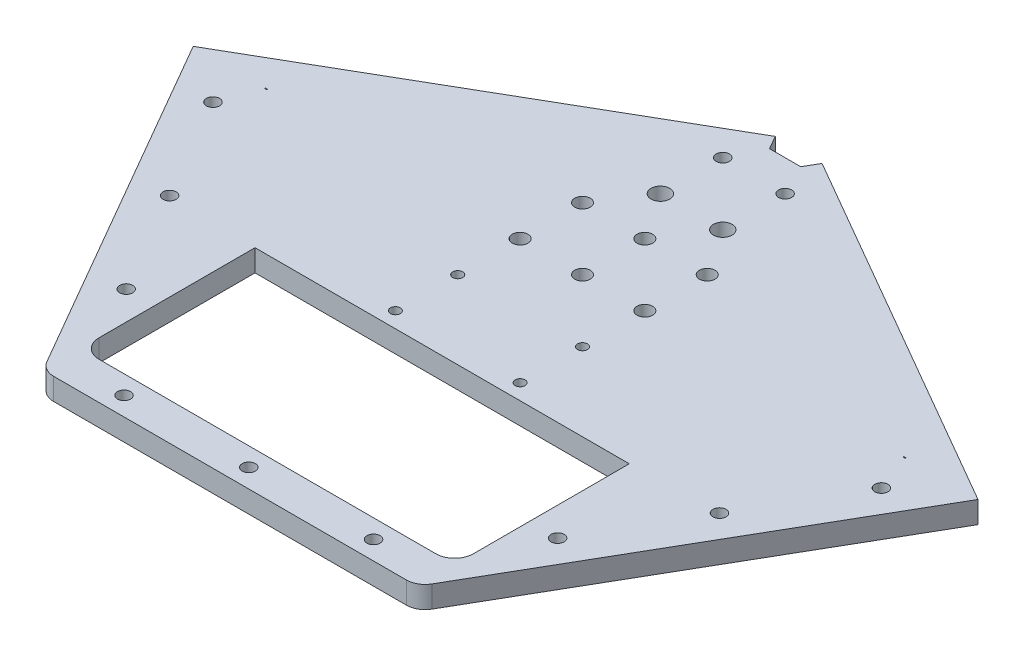
SolidWorks part; units mm, degrees
ref_plane "Front Plane" through (0, 0, 0) normal (0, 0, 1) x (1, 0, 0)
ref_plane "Top Plane" through (0, 0, 0) normal (0, 1, 0) x (1, 0, 0)
ref_plane "Right Plane" through (0, 0, 0) normal (1, 0, 0) x (0, 0, -1)
sketch "Sketch1" plane through (0, 0, 0) normal (0, 1, 0) x (1, 0, 0)
  line L15 (0, 28) -> (0, 74) construction
  line L16 (-60, -28) -> (60, -28)
  line L17 (-60, -28) -> (-60, 28)
  line L18 (-60, 28) -> (60, 28)
  line L19 (60, -28) -> (60, 28)
  line L20 (-60, -28) -> (60, 28) construction
  line L21 (-60, 28) -> (60, -28) construction
  line L27 (-20, 53) -> (-20, 33) construction
  line L31 (-20, 33) -> (0, 33) construction
  line L32 (-60, -40) -> (60, -40)
  line L33 (0, -40) -> (0, -28) construction
  line L34 (-60, -40) -> (-125.8179, 74)
  line L35 (-125.8179, 74) -> (125.8179, 74)
  line L36 (-125.8179, 74) -> (-191.6359, 188) construction
  line L37 (-191.6359, 188) -> (-131.6359, 291.923) construction
  line L38 (131.6359, 291.923) -> (191.6359, 188) construction
  line L39 (125.8179, 74) -> (191.6359, 188) construction
  line L40 (60, -40) -> (125.8179, 74)
  line L41 (87.7128, 48) -> (30, 48)
  line L42 (-131.6359, 291.923) -> (0, 291.923) construction
  line L48 (-125.8179, 74) -> (-108.4974, 84)
  line L49 (-108.4974, 84) -> (-87.7128, 48)
  line L50 (-87.7128, 48) -> (-30, 48)
  line L51 (-30, 48) -> (-30, 74)
  line L53 (-117.1577, 79) -> (-51.9171, -34) construction
  line L54 (-51.9171, -34) -> (0, -34) construction
  line L55 (0, 291.923) -> (131.6359, 291.923) construction
  line L62 (125.8179, 74) -> (108.4974, 84)
  line L63 (108.4974, 84) -> (87.7128, 48)
  line L64 (-161.6359, 239.9615) -> (0, 146.641) construction
  line L65 (-10, 107.9808) -> (10, 107.9808)
  line L66 (-10, 107.9808) -> (-10, 127.9808)
  line L67 (-10, 127.9808) -> (10, 127.9808)
  line L68 (10, 107.9808) -> (10, 127.9808)
  line L69 (-10, 107.9808) -> (10, 127.9808) construction
  line L70 (-10, 127.9808) -> (10, 107.9808) construction
  line L71 (0, 146.641) -> (161.6359, 239.9615) construction
  line L72 (30, 48) -> (30, 74)
  line L73 (0, 146.641) -> (0, -40) construction
  line L74 (-20, 112) -> (0, 146.641) construction
  line L75 (-20, 112) -> (20, 112)
  line L76 (20, 112) -> (40, 146.641)
  line L77 (40, 146.641) -> (20, 181.282)
  line L78 (20, 181.282) -> (-20, 181.282)
  line L79 (-20, 181.282) -> (-40, 146.641)
  line L80 (-40, 146.641) -> (-20, 112)
  line L81 (0, 146.641) -> (20, 181.282) construction
  line L82 (-20, 181.282) -> (0, 146.641) construction
  line L83 (0, 146.641) -> (20, 112) construction
  line L84 (-40, 146.641) -> (40, 146.641) construction
  line L85 (-30, 129.3205) -> (0, 146.641)
  line L86 (0, 146.641) -> (30, 129.3205)
  line L87 (0, 146.641) -> (0, 181.282) construction
  line L88 (-30, 129.3205) -> (-30, 74)
  line L89 (5, 137.9808) -> (10, 146.641)
  line L90 (10, 146.641) -> (5, 155.3013)
  line L91 (5, 155.3013) -> (-5, 155.3013)
  line L92 (-5, 155.3013) -> (-10, 146.641)
  line L93 (-10, 146.641) -> (-5, 137.9808)
  line L94 (-5, 137.9808) -> (5, 137.9808)
  line L95 (30, 129.3205) -> (30, 74)
  line L96 (-108.4974, 84) -> (-30, 129.3205)
  line L97 (-30, 115.4641) -> (-102.4974, 73.6077)
  line L98 (30, 129.3205) -> (108.4974, 84)
  line L99 (30, 115.4641) -> (102.4974, 73.6077)
  line L100 (-20, 73) -> (0, 73)
  line L101 (0, 73) -> (20, 73)
  line L102 (20, 73) -> (20, 93)
  line L103 (20, 93) -> (0, 93)
  line L104 (0, 93) -> (-20, 93)
  line L105 (-72.8179, -17.7987) -> (-55.4974, -7.7987) construction
  line L106 (-55.4974, -7.7987) -> (-55.4974, 28) construction
  line L107 (-60, -10.3983) -> (-60, 0)
  line L108 (-60, 0) -> (-87.7128, 48) construction
  line L109 (-55.4974, -7.7987) -> (-60, 0) construction
  circle A28 centre (-20, 33) radius 1.6
  circle A29 centre (-20, 53) radius 1.6
  circle A30 centre (20, 33) radius 1.6
  circle A31 centre (20, 53) radius 1.6
  circle A32 centre (0, 146.641) radius 34.641 construction
  circle A33 centre (-10, 127.9808) radius 2.1
  circle A34 centre (-10, 107.9808) radius 3
  circle A35 centre (10, 107.9808) radius 3
  circle A36 centre (10, 127.9808) radius 2.1
  circle A37 centre (-107.1577, 61.6795) radius 2.1
  circle A38 centre (0, -34) radius 2.1
  circle A39 centre (-40, -34) radius 2.1
  circle A40 centre (-69.1577, -4.1384) radius 2.1
  circle A41 centre (-88.1577, 28.7705) radius 2.1
  circle A42 centre (107.1577, 61.6795) radius 2.1
  circle A43 centre (88.1577, 28.7705) radius 2.1
  circle A44 centre (69.1577, -4.1384) radius 2.1
  circle A45 centre (40, -34) radius 2.1
  circle A46 centre (0, 146.641) radius 8.6603 construction
  circle A49 centre (-20, 73) radius 2.5
  circle A50 centre (20, 73) radius 2.5
  circle A51 centre (-20, 93) radius 2.5
  circle A52 centre (20, 93) radius 2.5
  circle A56 centre (0, 93) radius 2.5
  circle A57 centre (0, 73) radius 2.5
  point P0 (0, 0)
  point P33 (0, 117.9808)
  dimension "D2" = 20
  dimension "D16" = 20
  dimension "D20" = 10
  dimension "D21" = 4.2
  dimension "D31" = 5
  dimension "D34" = 4.5026
  dimension "D35" = 9.0052
  dimension "D3" = 3.2
  dimension "D17" = 4.2
  dimension "D18" = 6
  dimension "D22" = 20
  dimension "D23" = 38
  dimension "D24" = 38
  dimension "D25" = 40
  dimension "D29" = 20
  dimension "D1" = 5
  dimension "D4" = 120
  dimension "D5" = 56
  dimension "D6" = 20
  dimension "D7" = 12
  dimension "D8" = 10
  dimension "D9" = 20
  dimension "D10" = 30
  dimension "D11" = 26
  dimension "D12" = 120
  dimension "D13" = 120
  dimension "D14" = 251.6359
  dimension "D15" = 20
  dimension "D19" = 40
  dimension "D26" = 10
  dimension "D27" = 12
  dimension "D28" = 12
  dimension "D30" = 20
  dimension "D32" = 10
  dimension "D33" = 20
  dimension "D36" = 5.1991
  dimension "D37" = 10.3983
  dimension "D38" = 130.4812
  dimension "D39" = 51.9171
extrude "Boss-Extrude1" add sketch "Sketch1" along normal blind 7 contours A35 L65 A34 L66 L75 L80 L88 L35 L95 L76 L68 | L97 L88 L96 L49 L35 | A36 L68 L75 L76 L86 L89 L94 L93 L85 L80 L66 A33 L67 | A36 L67 A33 L66 L75 L68 | L95 L99 L35 L63 L98 | A35 L68 L75 L66 A34 L65 | L41 L72 L35 L51 L50 L49 L34 L32 L40 L63 A44 A42 A41 A40 A39 A38 A37 A30 A29 A28 L19 L16 L17 L18 A31 A43 A45 | L62 L63 L35 | L49 L48 L35 | A57 L35 A49 L100 | A57 L101 A50 L35 | L88 L97 L35 | L35 L97 L49 L50 L51 | L99 L95 L35 | L99 L35 L72 L41 L63 region at (-90.5165, 0, -18.3813) region at (-112.3464, 0, -77.3333) region at (112.3464, 0, -77.3333) region at (-67.7627, 0, -100.6829) region at (67.7627, 0, -100.6829) region at (-53.9393, 0, -87.8214) region at (-62.749, 0, -61.4974) region at (-18.4139, 0, -135.2335) region at (-25.7068, 0, -120.2522) region at (62.749, 0, -61.4974) region at (53.9393, 0, -87.8214) region at (0, 0, -110.1475) region at (0, 0, -119.8331) region at (-10, 0, -73.5023) region at (10, 0, -73.5023)
fillet "Fillet1" radius 6 4 edges at (-60, 3.5, 28) (60, 3.5, 28) (60, 3.5, 40) (-60, 3.5, 40)
